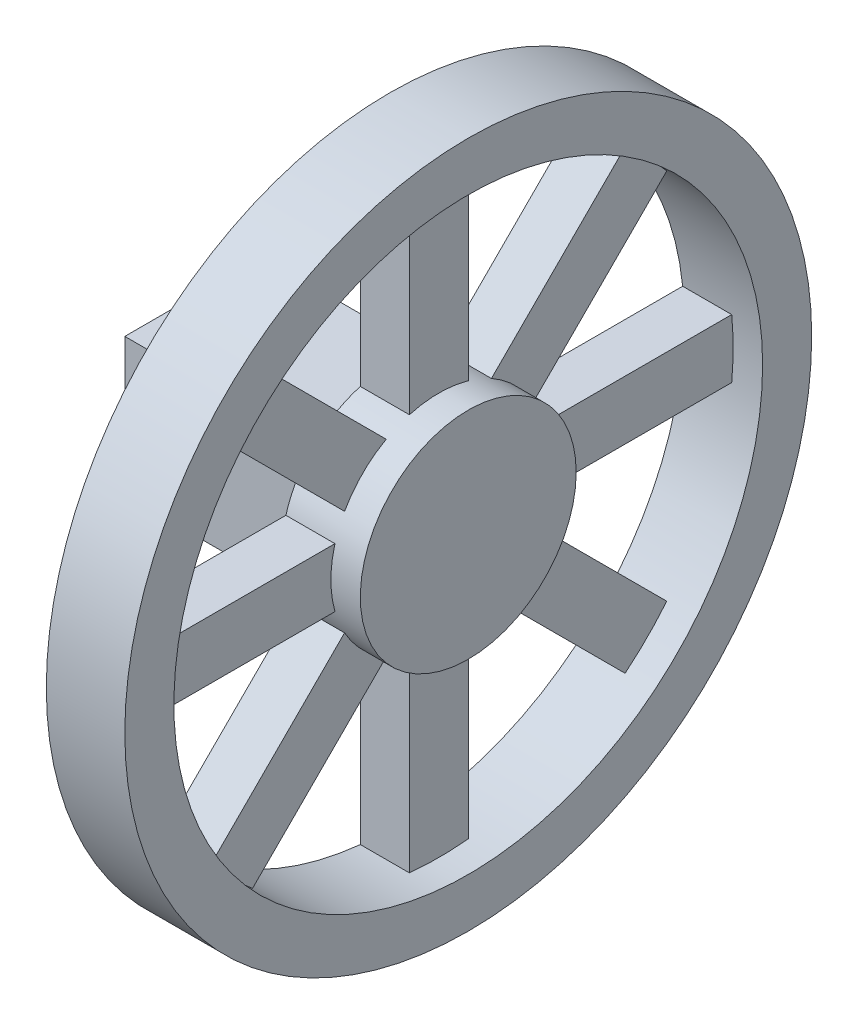
SolidWorks part; units mm, degrees
material "Commercialement pur CP-Ti UNS R50400 (SS)"
ref_plane "Plan de face" through (0, 0, 0) normal (0, 0, 1) x (1, 0, 0)
ref_plane "Plan de dessus" through (0, 0, 0) normal (0, 1, 0) x (1, 0, 0)
ref_plane "Plan de droite" through (0, 0, 0) normal (1, 0, 0) x (0, 0, -1)
sketch "Esquisse1" plane through (0, 0, 0) normal (1, 0, 0) x (0, 0, -1)
  line L1 (-35, -35) -> (35, -35)
  line L2 (-35, -35) -> (-35, 35)
  line L3 (-35, 35) -> (35, 35)
  line L4 (35, -35) -> (35, 35)
  line L5 (-35, -35) -> (35, 35) construction
  line L6 (-35, 35) -> (35, -35) construction
  point P0 (0, 0)
  dimension "D1" = 70
  dimension "D2" = 70
extrude "Boss.-Extru.1" add sketch "Esquisse1" along normal blind 100
sketch "Esquisse2" plane through (100, 0, 0) normal (1, 0, 0) x (0, 0, -1)
  line L0 (0, 55) -> (0, 150)
  line L1 (-15, 52.915) -> (-15, 149.2481)
  line L2 (15, 52.915) -> (15, 149.2481)
  line L3 (26.81, 48.0232) -> (94.9278, 116.141)
  line L4 (48.0232, 26.81) -> (116.141, 94.9278)
  line L5 (52.915, 15) -> (149.2481, 15)
  line L6 (52.915, -15) -> (149.2481, -15)
  line L7 (48.0232, -26.81) -> (116.141, -94.9278)
  line L8 (26.81, -48.0232) -> (94.9278, -116.141)
  line L9 (15, -52.915) -> (15, -149.2481)
  line L10 (-15, -52.915) -> (-15, -149.2481)
  line L11 (-26.81, -48.0232) -> (-94.9278, -116.141)
  line L12 (-48.0232, -26.81) -> (-116.141, -94.9278)
  line L13 (-52.915, -15) -> (-149.2481, -15)
  line L14 (-52.915, 15) -> (-149.2481, 15)
  line L15 (-48.0232, 26.81) -> (-116.141, 94.9278)
  line L16 (-26.81, 48.0232) -> (-94.9278, 116.141)
  circle A0 centre (0, 0) radius 150
  circle A1 centre (0, 0) radius 175
  circle A2 centre (0, 0) radius 55
  point P42 (0, 0)
  line M4 (35, -35) -> (35, 35)
  line M5 (35, 35) -> (-35, 35)
  line M6 (-35, 35) -> (-35, -35)
  line M7 (-35, -35) -> (35, -35)
  dimension "D1" = 300
  dimension "D2" = 350
  dimension "D3" = 110
  dimension "D4" = 15
  dimension "D5" = 15
  dimension "D6" = 8
extrude "Boss.-Extru.2" add sketch "Esquisse2" along normal blind 40 separate body contours A1 A0 | A2 M4 M7 M6 M5 | A2 region at (100, 52.9354, -7.3579) region at (100, 0, 170.0503)
extrude "Boss.-Extru.3" add sketch "Esquisse2<3>" along normal blind 25 contours A2 L16 A0 L15 | A2 L2 A0 L0 | A2 L0 A0 L1 | A2 L4 A0 L3 | A2 L6 A0 L5 | A2 L8 A0 L7 | A2 L10 A0 L9 | A2 L12 A0 L11 | A2 L14 A0 L13 region at (100, 102.0282, 7.5174) region at (100, 102.0282, -7.5174) region at (100, 72.1449, -72.1449) region at (100, 72.1449, 72.1449) region at (100, 0, -102.0282) region at (100, 0, 102.0282) region at (100, -72.1449, 72.1449) region at (100, -72.1449, -72.1449) region at (100, -102.0282, 0)
sketch "Esquisse2<3>" plane through (100, 0, 0) normal (1, 0, 0) x (0, 0, -1) same geometry as "Esquisse2"
